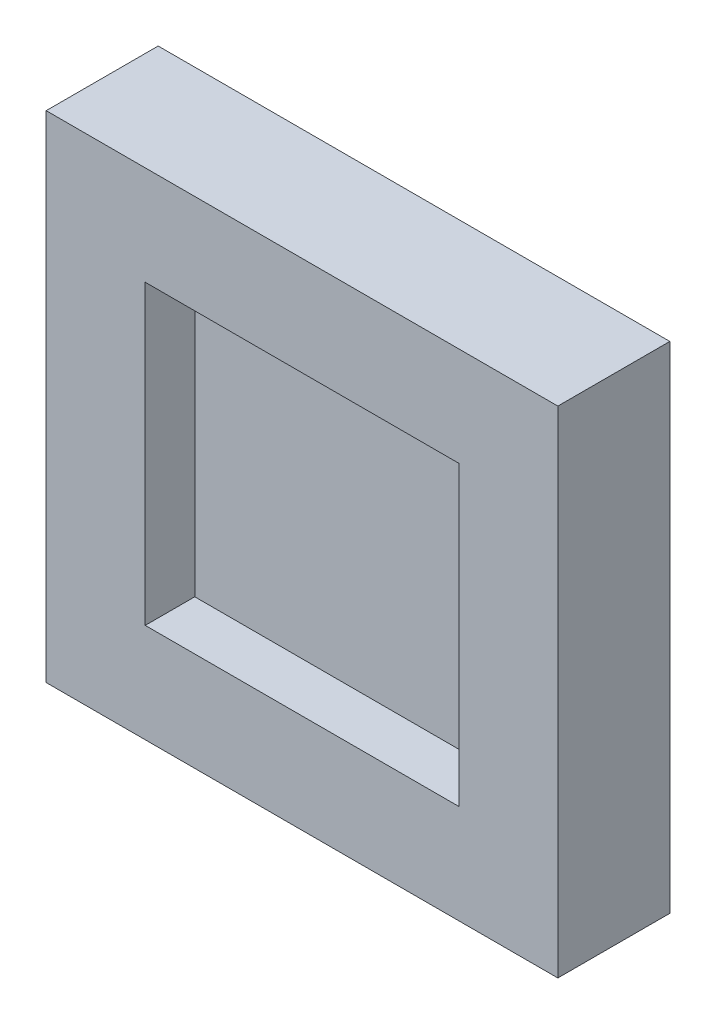
SolidWorks part; units mm, degrees
ref_plane "Plano frontal" through (0, 0, 0) normal (0, 0, 1) x (1, 0, 0)
ref_plane "Plano superior" through (0, 0, 0) normal (0, 1, 0) x (1, 0, 0)
ref_plane "Plano direito" through (0, 0, 0) normal (1, 0, 0) x (0, 0, -1)
sketch "Esboço1" plane through (0, 0, 0) normal (0, 0, 1) x (1, 0, 0)
  line L1 (182, 172.5) -> (-182, 172.5)
  line L2 (182, 172.5) -> (182, -172.5)
  line L3 (182, -172.5) -> (-182, -172.5)
  line L4 (-182, 172.5) -> (-182, -172.5)
  line L5 (182, 172.5) -> (-182, -172.5) construction
  line L6 (182, -172.5) -> (-182, 172.5) construction
  point P0 (0, 0)
  dimension "D1" = 345
  dimension "D2" = 364
extrude "Ressalto-extrusão1" add sketch "Esboço1" along normal blind 7.5 and the other way blind 7.5
sketch "Esboço2" plane through (0, 0, 0) normal (0, 0, 1) x (1, 0, 0)
  line L1 (182, 172.5) -> (-182, 172.5)
  line L2 (182, 172.5) -> (182, -172.5)
  line L3 (182, -172.5) -> (-182, -172.5)
  line L4 (-182, 172.5) -> (-182, -172.5)
  line L5 (182, 172.5) -> (-182, -172.5) construction
  line L6 (182, -172.5) -> (-182, 172.5) construction
  line L14 (-297, 287.5) -> (-297, -287.5)
  line L15 (-297, -287.5) -> (297, -287.5)
  line L16 (297, -287.5) -> (297, 287.5)
  line L17 (297, 287.5) -> (-297, 287.5)
  line L18 (-297, 287.5) -> (-297, -287.5)
  line L19 (-297, -287.5) -> (297, -287.5)
  line L20 (297, -287.5) -> (297, 287.5)
  line L21 (297, 287.5) -> (-297, 287.5)
  point P0 (0, 0)
  dimension "D1" = 115
extrude "Ressalto-extrusão2" add sketch "Esboço2" along normal blind 65 and the other way blind 65 separate body
